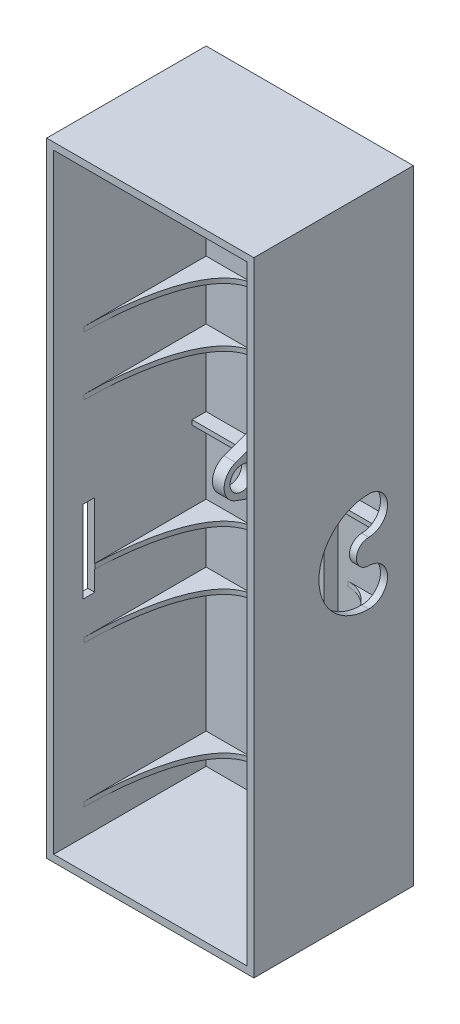
SolidWorks part; units mm, degrees
ref_plane "Front Plane" through (0, 0, 0) normal (0, 0, 1) x (1, 0, 0)
ref_plane "Top Plane" through (0, 0, 0) normal (0, 1, 0) x (1, 0, 0)
ref_plane "Right Plane" through (0, 0, 0) normal (1, 0, 0) x (0, 0, -1)
sketch "Sketch1" plane through (0, 0, 0) normal (0, 0, 1) x (1, 0, 0)
  line L0 (0, 263) -> (0, 0)
  line L1 (0, 0) -> (88.35, 0)
  line L3 (3, 3) -> (85.35, 3)
  line L7 (0, 263) -> (3, 263)
  line L8 (3, 3) -> (3, 263)
  line L11 (85.35, 3) -> (85.35, 263.0928)
  line L12 (85.35, 263.0928) -> (88.35, 263.0928)
  line L13 (88.35, 0) -> (88.35, 263.0928)
  dimension "D1" = 3
  dimension "D2" = 3
  dimension "D3" = 260
  dimension "D4" = 82.35
  dimension "D5" = 3
extrude "Boss-Extrude1" add sketch "Sketch1" along normal blind 68
sketch "Sketch2" plane through (0, 0, 0) normal (0, 0, 1) x (1, 0, 0)
  line L1 (0, 263) -> (88.35, 263)
  line L2 (0, 263) -> (0, 0)
  line L3 (0, 0) -> (88.35, 0)
  line L4 (88.35, 263) -> (88.35, 0)
extrude "Boss-Extrude2" add sketch "Sketch2" along normal blind 3
ref_plane "Plane1" through (34.175, 0, 0) normal (1, 0, 0) x (0, 0, -1)
sketch "Sketch3" plane through (34.175, 0, 0) normal (1, 0, 0) x (0, 0, -1)
  line L2 (-21.5652, 140.0477) -> (-3, 146.8049)
  line L3 (-3, 3) -> (-3, 263) construction
  line L4 (-3, 146.8049) -> (-3, 119.1951)
  line L5 (-3, 119.1951) -> (-21.5652, 125.9523)
  line L7 (-68, 3) -> (-3, 3) construction
  arc A0 (-21.5652, 140.0477) -> (-21.5652, 125.9523) centre (-19, 133) ccw
  circle A1 centre (-19, 133) radius 5
  dimension "D2" = 15
  dimension "D5" = 10
  dimension "D1" = 16
  dimension "D3" = 130
  dimension "D4" = 70
extrude "Boss-Extrude3" add sketch "Sketch3" against normal blind 5
ref_plane "Plane2" through (54.175, 0, 0) normal (1, 0, 0) x (0, 0, -1)
sketch "Sketch6" plane through (54.175, 0, 0) normal (1, 0, 0) x (0, 0, -1)
  line L0 (-19, 138) -> (-3, 138)
  line L2 (-3, 138) -> (-3, 128)
  line L3 (-3, 128) -> (-19, 128)
  line L4 (-3, 263) -> (-3, 3) construction
  arc A0 (-19, 138) -> (-19, 128) centre (-19, 133) ccw
  circle A1 centre (-19, 133) radius 5 construction
extrude "Boss-Extrude6" add sketch "Sketch6" along normal blind 8
hole_wizard "M6 Clearance Hole1" positions "Sketch7" profile "Sketch8" hole size "M6" standard "ISO" end condition up to next
sketch "Sketch7" plane through (54.175, 0, 0) normal (-1, 0, 0) x (0, 0, 1)
  arc A0 (19, 128) -> (19, 138) centre (19, 133) ccw construction
  point P0 (19, 133)
sketch "Sketch8" plane through (54.175, 133, 19) normal (0, 1, 0) x (0, 0, 1)
  line L0 (0, 0) -> (0, 8)
  line L1 (0, 8) -> (3.3, 8)
  line L2 (3.3, 8) -> (3.3, 0)
  line L5 (3.3, 0) -> (0, 0)
  line L11 (0, -6.35) -> (0, 107.95) construction
  dimension "Thru Hole Dia." = 6.6
  dimension "Thru Hole Depth" = 8
sketch "Sketch10" plane through (85.35, 0, 0) normal (-1, 0, 0) x (0, 0, 1)
  line L2 (3, 263) -> (3, 3) construction
  line L4 (19, 146.25) -> (19, 119.75) construction
  arc A0 (19, 146.25) -> (19, 119.75) centre (19, 133) cw construction
  arc A1 (19, 111.75) -> (19, 154.25) centre (19, 133) ccw
  arc A2 (19, 127.75) -> (19, 138.25) centre (19, 133) ccw
  arc A3 (19, 127.75) -> (19, 111.75) centre (19, 119.75) ccw
  arc A4 (19, 154.25) -> (19, 138.25) centre (19, 146.25) ccw
  point P5 (32.25, 133)
  point P20 (3, 133)
  dimension "D3" = 8
  dimension "D1" = 16
  dimension "D2" = 13.25
extrude "Cut-Extrude1" cut sketch "Sketch10" against normal up to next
sketch "Sketch11" plane through (0, 263, 0) normal (0, 1, 0) x (1, 0, 0)
  line L4 (0, 0) -> (0, -68)
  line L5 (88.35, 0) -> (0, 0)
  line L6 (88.35, -68) -> (88.35, 0)
  line L7 (0, -68) -> (88.35, -68)
  line L8 (0, 0) -> (0, -68)
  line L9 (88.35, 0) -> (0, 0)
  line L10 (88.35, -68) -> (88.35, 0)
  line L11 (0, -68) -> (88.35, -68)
  dimension "D1" = 0
extrude "Boss-Extrude7" add sketch "Sketch11" along normal blind 3
ref_plane "Plane4" through (44.175, 0, 0) normal (1, 0, 0) x (0, 0, -1)
sketch "Sketch13" plane through (0, 0, 3) normal (0, 0, 1) x (1, 0, 0)
  line L0 (3, 3) -> (3, 263) construction
  line L1 (3, 251.9797) -> (24.8525, 251.9797)
  line L2 (3, 251.9797) -> (3, 249.9797)
  line L3 (3, 249.9797) -> (24.8525, 249.9797)
  line L4 (24.8525, 251.9797) -> (24.8525, 249.9797)
  line L5 (3, 3) -> (3, 263) construction
  line L6 (3, 191.4189) -> (24.8525, 191.4189)
  line L7 (3, 191.4189) -> (3, 189.4189)
  line L8 (3, 189.4189) -> (24.8525, 189.4189)
  line L9 (24.8525, 191.4189) -> (24.8525, 189.4189)
  line L10 (3, 166.3498) -> (24.8525, 166.3498)
  line L11 (3, 166.3498) -> (3, 164.3498)
  line L12 (3, 164.3498) -> (24.8525, 164.3498)
  line L13 (24.8525, 166.3498) -> (24.8525, 164.3498)
  line L14 (3, 133) -> (85.35, 133) construction
  line L15 (85.35, 263) -> (85.35, 3) construction
  line L16 (3, 16.0203) -> (24.8525, 16.0203)
  line L17 (24.8525, 14.0203) -> (24.8525, 16.0203)
  line L18 (3, 14.0203) -> (24.8525, 14.0203)
  line L19 (3, 14.0203) -> (3, 16.0203)
  line L20 (3, 76.5811) -> (24.8525, 76.5811)
  line L21 (24.8525, 74.5811) -> (24.8525, 76.5811)
  line L22 (3, 74.5811) -> (24.8525, 74.5811)
  line L23 (3, 74.5811) -> (3, 76.5811)
  line L24 (3, 101.6502) -> (24.8525, 101.6502)
  line L25 (24.8525, 99.6502) -> (24.8525, 101.6502)
  line L26 (3, 99.6502) -> (24.8525, 99.6502)
  line L27 (3, 99.6502) -> (3, 101.6502)
  dimension "D1" = 2
extrude "Boss-Extrude8" add sketch "Sketch13" along normal blind 52
sketch "Sketch14" plane through (0, 14.0203, 0) normal (0, -1, 0) x (1, 0, 0)
  line L0 (3, 3) -> (24.8525, 3) construction
  line L1 (3, 55) -> (3, 3) construction
  line L2 (24.8525, 3) -> (24.8525, 55)
  line L3 (24.8525, 55) -> (3, 55)
  spline S0 degree 3 poles (3, 55) (3, 38.0721) (6.2716, 3) (24.8525, 3) knots 0 0 0 0 1 1 1 1
extrude "Cut-Extrude2" cut sketch "Sketch14" against normal up to surface (237.9595 mm away) up to face at (13.9263, 251.9797, 29)
mirror "Mirror3" about plane through (44.175, 0, 0) normal (1, 0, 0) of "Boss-Extrude8", "Cut-Extrude2"
sketch "Sketch15" plane through (0, 0, 3) normal (0, 0, 1) x (1, 0, 0)
  line L0 (85.35, 263) -> (3, 263) construction
  line L1 (30.675, 263) -> (32.675, 263)
  line L2 (30.675, 263) -> (30.675, 3)
  line L3 (30.675, 3) -> (32.675, 3)
  line L4 (32.675, 263) -> (32.675, 3)
  line L5 (85.35, 3) -> (3, 3) construction
  line L6 (29.175, 119.1951) -> (34.175, 119.1951) construction
  line L7 (3, 263) -> (85.35, 263) construction
  line L8 (59.175, 263) -> (57.175, 263)
  line L9 (59.175, 263) -> (59.175, 3)
  line L10 (59.175, 3) -> (57.175, 3)
  line L11 (57.175, 263) -> (57.175, 3)
  line L12 (62.175, 128) -> (54.175, 128) construction
  line L13 (29.175, 119.1951) -> (29.175, 146.8049) construction
  line L14 (29.175, 134) -> (3, 134)
  line L15 (29.175, 134) -> (29.175, 132)
  line L16 (29.175, 132) -> (3, 132)
  line L17 (3, 134) -> (3, 132)
  line L18 (3, 101.6502) -> (3, 164.3498) construction
  line L19 (62.175, 128) -> (62.175, 138) construction
  line L20 (62.175, 134) -> (85.35, 134)
  line L21 (62.175, 134) -> (62.175, 132)
  line L22 (62.175, 132) -> (85.35, 132)
  line L23 (85.35, 134) -> (85.35, 132)
  line L24 (85.35, 263) -> (85.35, 3) construction
  line L25 (29.175, 140.0477) -> (29.175, 125.9523) construction
  point P10 (31.675, 119.1951)
  point P11 (31.675, 3)
  point P18 (58.175, 3)
  point P21 (58.175, 128)
  point P38 (62.175, 133)
  point P39 (29.175, 133)
  dimension "D1" = 2
extrude "Boss-Extrude9" add sketch "Sketch15" along normal blind 6
sketch "Sketch16" plane through (0, 0, 3) normal (0, 0, 1) x (1, 0, 0)
  line L1 (36.675, 258) -> (51.675, 258)
  line L2 (36.675, 258) -> (36.675, 208)
  line L3 (36.675, 208) -> (51.675, 208)
  line L4 (51.675, 258) -> (51.675, 208)
  line L5 (54.175, 138) -> (54.175, 128) construction
  line L7 (34.175, 133) -> (54.175, 133) construction
  line L8 (34.175, 119.1951) -> (34.175, 146.8049) construction
  line L9 (36.675, 58) -> (51.675, 58)
  line L10 (51.675, 8) -> (51.675, 58)
  line L11 (36.675, 8) -> (51.675, 8)
  line L12 (36.675, 8) -> (36.675, 58)
  line L13 (88.35, 266) -> (0, 266) construction
  point P10 (54.175, 133)
  point P11 (51.675, 233)
  point P20 (44.175, 266)
  point P21 (44.175, 258)
  dimension "D1" = 15
  dimension "D2" = 50
  dimension "D3" = 100
extrude "Boss-Extrude10" add sketch "Sketch16" along normal blind 4
hole_wizard "M6 Tapped Hole2" positions "Sketch17" profile "Sketch18" tap size "M6" standard "ISO" end condition up to next
sketch "Sketch17" plane through (0, 0, 7) normal (0, 0, 1) x (1, 0, 0)
  line L0 (51.675, 258) -> (36.675, 258) construction
  line L1 (36.675, 208) -> (51.675, 208) construction
  line L2 (51.675, 58) -> (36.675, 58) construction
  line L3 (36.675, 8) -> (51.675, 8) construction
  point P0 (44.175, 250.24)
  point P2 (44.175, 215.76)
  point P4 (44.175, 50.24)
  point P6 (44.175, 15.76)
  point P18 (44.175, 8)
  dimension "D1" = 7.76
  dimension "D2" = 7.76
  dimension "D3" = 7.76
  dimension "D4" = 7.76
sketch "Sketch18" plane through (44.175, 250.24, 7) normal (1, 0, 0) x (0, -1, 0)
  line L0 (0, 0) -> (0, 7)
  line L1 (0, 7) -> (2.5, 7)
  line L2 (2.5, 7) -> (2.5, 0)
  line L5 (2.5, 0) -> (0, 0)
  line L11 (0, -6.35) -> (0, 107.95) construction
  dimension "Thru Tap Drill Dia." = 5
  dimension "Thru Tap Drill Depth" = 7
cosmetic thread "Hole Thread2" parameters "D2"=6
cosmetic thread "Hole Thread3" parameters "D2"=6
cosmetic thread "Hole Thread4" parameters "D2"=6
cosmetic thread "Hole Thread5" parameters "D2"=6
sketch "Sketch20" plane through (3, 0, 0) normal (1, 0, 0) x (0, 0, -1)
  line L0 (-68, 3) -> (-68, 263) construction
  line L1 (-55.5, 126) -> (-50.5, 126)
  line L2 (-55.5, 126) -> (-55.5, 91)
  line L3 (-55.5, 91) -> (-50.5, 91)
  line L4 (-50.5, 126) -> (-50.5, 91)
  line L5 (0, 266) -> (-68, 266) construction
  dimension "D1" = 35
  dimension "D2" = 12.5
  dimension "D3" = 5
  dimension "D4" = 140
extrude "Cut-Extrude4" cut sketch "Sketch20" against normal mid plane 20
